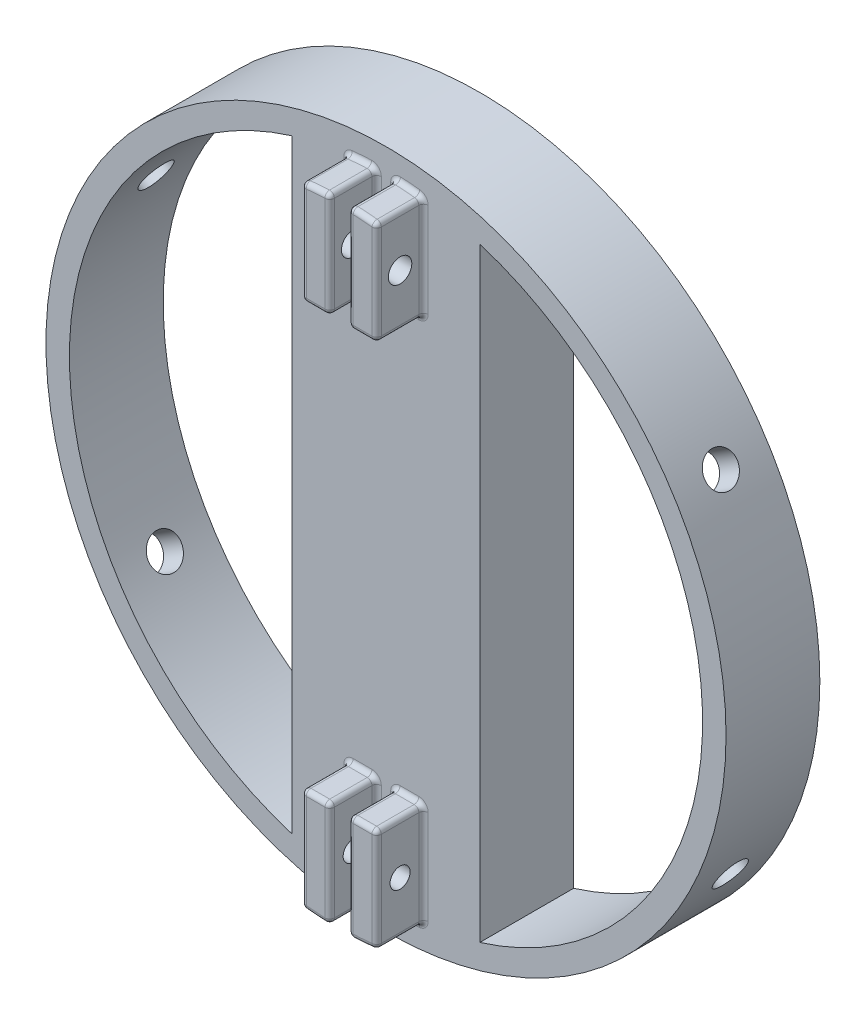
SolidWorks part; units mm, degrees
ref_plane "Front Plane" through (0, 0, 0) normal (0, 0, 1) x (1, 0, 0)
ref_plane "Top Plane" through (0, 0, 0) normal (0, 1, 0) x (1, 0, 0)
ref_plane "Right Plane" through (0, 0, 0) normal (1, 0, 0) x (0, 0, -1)
sketch "Sketch5" plane through (0, 0, 0) normal (0, 0, 1) x (1, 0, 0)
  circle A0 centre (0, 0) radius 36.25
  dimension "D1" = 72.5
extrude "Boss-Extrude2" add sketch "Sketch5" along normal blind 10
sketch "Sketch6" plane through (0, 0, 10) normal (0, 0, 1) x (1, 0, 0)
  line L0 (10, 32.2345) -> (10, -32.2345)
  line L1 (-10, 32.2345) -> (-10, -32.2345)
  line L2 (4, 33.5121) -> (4, 22.5)
  line L3 (-4, 33.5121) -> (-4, 22.5)
  line L4 (1, 33.7352) -> (1, 22.5)
  line L5 (-1, 33.7352) -> (-1, 22.5)
  line L6 (-4, 22.5) -> (-1, 22.5)
  line L7 (-4, -22.5) -> (-1, -22.5)
  line L8 (1, -22.5) -> (1, -33.7352)
  line L9 (4, -22.5) -> (4, -33.5121)
  line L10 (-1, -22.5) -> (-1, -33.7352)
  line L11 (-4, -22.5) -> (-4, -33.5121)
  line L12 (1, 22.5) -> (4, 22.5)
  line L13 (1, -22.5) -> (4, -22.5)
  arc A0 (-1, 33.7352) -> (-4, 33.5121) centre (0, 0) ccw
  arc A1 (1, -33.7352) -> (4, -33.5121) centre (0, 0) ccw
  arc A2 (10, -32.2345) -> (10, 32.2345) centre (0, 0) ccw
  arc A3 (-4, -33.5121) -> (-1, -33.7352) centre (0, 0) ccw
  arc A4 (-10, 32.2345) -> (-10, -32.2345) centre (0, 0) ccw
  arc A5 (4, 33.5121) -> (1, 33.7352) centre (0, 0) ccw
  point P7 (10, 0)
  point P8 (-10, 0)
  dimension "D1" = 67.5
  dimension "D2" = 10
  dimension "D3" = 10
  dimension "D4" = 4
  dimension "D5" = 4
  dimension "D6" = 1
  dimension "D7" = 1
  dimension "D8" = 22.5
  dimension "D9" = 22.5
extrude "Cut-Extrude1" cut sketch "Sketch6" against normal blind 10 contours L0 A0 | L1 A0 region at (19.8614, 0, 10) region at (-19.8614, 0, 10)
extrude "Boss-Extrude4" add sketch "Sketch6<8>" along normal blind 5 contours L11 A3 L10 L7 | L8 A1 L9 L13 | L5 A0 L3 L6 | L2 L12 L4 A5 region at (-2.495, 28.0732, 10) region at (-2.495, -28.0732, 10) region at (2.495, -28.0732, 10)
sketch "Sketch6<8>" plane through (0, 0, 10) normal (0, 0, 1) x (1, 0, 0) same geometry as "Sketch6"
fillet "Fillet1" radius 0.5 48 edges at (1, -28.1176, 10) (1, 28.1176, 10) (-1, 28.1176, 10) (4, 28.0061, 10) (-2.5, -22.5, 10) (1, -22.5, 12.5) (2.5, -22.5, 10) (-2.5, -22.5, 15) (-1, -28.1176, 15) (-1, -22.5, 12.5) (-1, -28.1176, 10) (2.5, -22.5, 15) (1, -28.1176, 15) (4, -28.0061, 15) (4, -22.5, 12.5) (4, -28.0061, 10) (1, -33.7352, 12.5) (2.5025, -33.6571, 15) (4, -33.5121, 12.5) (2.5025, -33.6571, 10) (-2.5025, -33.6571, 15) (-1, -33.7352, 12.5) (-2.5025, -33.6571, 10) (-4, -22.5, 12.5) (-4, -28.0061, 15) (-4, -33.5121, 12.5) (-4, -28.0061, 10) (-1, 22.5, 12.5) (-2.5, 22.5, 10) (1, 22.5, 12.5) (4, 22.5, 12.5) (2.5, 22.5, 10) (-4, 22.5, 12.5) (-4, 28.0061, 10) (4, 33.5121, 12.5) (1, 33.7352, 12.5) (2.5025, 33.6571, 10) (-1, 33.7352, 12.5) (-4, 33.5121, 12.5) (-2.5025, 33.6571, 10) (4, 28.0061, 15) (2.5, 22.5, 15) (1, 28.1176, 15) (2.5025, 33.6571, 15) (-2.5, 22.5, 15) (-4, 28.0061, 15) (-2.5025, 33.6571, 15) (-1, 28.1176, 15)
ref_plane "Plane2" through (31.7036, -17.5768, 0) normal (0.8746, -0.4849, 0) x (0, 0, -1)
sketch "Sketch8" plane through (31.7036, -17.5768, 0) normal (0.8746, -0.4849, 0) x (0, 0, -1)
  line L0 (-10, 36.25) -> (-10, -36.25) construction
  circle A0 centre (-5, 0) radius 1.75
  dimension "D2" = 3.5
  dimension "D1" = 5
extrude "Cut-Extrude2" cut sketch "Sketch8" against normal blind 5
ref_plane "Plane3" through (30.7029, 19.2717, 0) normal (0.847, 0.5316, 0) x (0, 0, -1)
sketch "Sketch9" plane through (30.7029, 19.2717, 0) normal (0.847, 0.5316, 0) x (0, 0, -1)
  line L0 (-10, 36.25) -> (-10, -36.25) construction
  circle A0 centre (-5, 0) radius 1.75
  dimension "D1" = 3.5
  dimension "D2" = 5
extrude "Cut-Extrude3" cut sketch "Sketch9" against normal blind 5
ref_plane "Plane4" through (-31.7036, 17.5768, 0) normal (-0.8746, 0.4849, 0) x (0, 0, 1)
sketch "Sketch10" plane through (-31.7036, 17.5768, 0) normal (-0.8746, 0.4849, 0) x (0, 0, 1)
  line L0 (10, -36.25) -> (10, 36.25) construction
  circle A0 centre (5, 0) radius 1.75
  dimension "D1" = 3.5
  dimension "D2" = 5
extrude "Cut-Extrude4" cut sketch "Sketch10" against normal blind 5
ref_plane "Plane5" through (-30.7029, -19.2717, 0) normal (-0.847, -0.5316, 0) x (0, 0, 1)
sketch "Sketch11" plane through (-30.7029, -19.2717, 0) normal (-0.847, -0.5316, 0) x (0, 0, 1)
  line L0 (10, -36.25) -> (10, 36.25) construction
  circle A0 centre (5, 0) radius 1.75
  dimension "D1" = 3.5
  dimension "D2" = 5
extrude "Cut-Extrude5" cut sketch "Sketch11" against normal blind 5
sketch "Sketch12" plane through (4, 0, 0) normal (1, 0, 0) x (0, 0, -1)
  line L1 (-14.5, 33.0653) -> (-14.5, 23) construction
  line L2 (-10.5, 33.0653) -> (-14.5, 33.0653) construction
  circle A0 centre (-12.5, 28.0653) radius 1.25
  dimension "D1" = 2.5
  dimension "D2" = 2
  dimension "D3" = 5
extrude "Cut-Extrude6" cut sketch "Sketch12" against normal blind 10
sketch "Sketch13" plane through (4, 0, 0) normal (1, 0, 0) x (0, 0, -1)
  line L0 (-14.5, -23) -> (-14.5, -33.0653) construction
  line L1 (-10.5, -23) -> (-14.5, -23) construction
  circle A0 centre (-12.5, -28) radius 1.0678
  dimension "D1" = 2.1356
  dimension "D2" = 2
  dimension "D3" = 5
extrude "Cut-Extrude7" cut sketch "Sketch13" against normal blind 10
